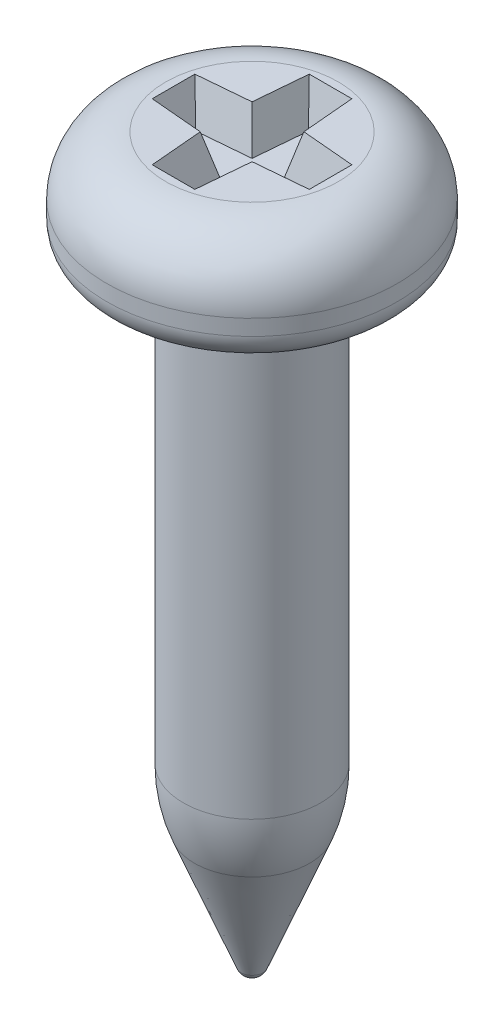
SolidWorks part; units mm, degrees
ref_plane "Front Plane" through (0, 0, 0) normal (0, 0, 1) x (1, 0, 0)
ref_plane "Top Plane" through (0, 0, 0) normal (0, 1, 0) x (1, 0, 0)
ref_plane "Right Plane" through (0, 0, 0) normal (1, 0, 0) x (0, 0, -1)
sketch "Sketch1" plane through (0, 0, 0) normal (0, 0, 1) x (1, 0, 0)
  line L0 (0, 0) -> (0, -9.3) construction
  line L2 (0.875, -6.9644) -> (0.875, -1.45)
  line L3 (1.025, -1.3) -> (1.5, -1.3)
  line L4 (1.85, -0.95) -> (1.85, -0.75)
  line L5 (1.1, 0) -> (0, 0)
  line L6 (0, 0) -> (0, -9.3)
  line L7 (0.7348, -7.7) -> (0.1395, -9.2052)
  arc A0 (1.85, -0.75) -> (1.1, 0) centre (1.1, -0.75) ccw
  arc A1 (1.5, -1.3) -> (1.85, -0.95) centre (1.5, -0.95) ccw
  arc A2 (0.875, -1.45) -> (1.025, -1.3) centre (1.025, -1.45) cw
  arc A3 (0.1395, -9.2052) -> (0, -9.3) centre (0, -9.15) cw
  arc A4 (0.7348, -7.7) -> (0.875, -6.9644) centre (-1.125, -6.9644) ccw
  point P3 (0, 0)
  point P13 (0.875, -1.3)
  point P19 (0, 0)
  point P20 (0, 0)
  point P21 (0, 0)
  point P22 (0.5012, -7.2)
  point P23 (0, 0)
  point P24 (0.9544, -3.2254)
  point P25 (0.8362, -7.4591)
  dimension "D3" = 0.75
  dimension "D6" = 0.35
  dimension "D7" = 0.15
  dimension "D8" = 2
  dimension "D4" = 1.6
  dimension "D10" = 0.15
  dimension "D1" = 3.7
  dimension "D2" = 1.3
  dimension "D5" = 1.75
  dimension "D9" = 8
revolve "Revolve1" add sketch "Sketch1" angle 360 about L0
sketch "Sketch2" plane through (0, 0, 0) normal (0, 1, 0) x (1, 0, 0)
  line L0 (0, 1) -> (0, 0) construction
  line L1 (0, 0) -> (1, 0) construction
  line L2 (-0.2714, 1) -> (0.2714, 1)
  line L3 (0.2714, 1) -> (0.33, 0.33)
  line L4 (0.33, 0.33) -> (1, 0.2714)
  line L5 (1, 0.2714) -> (1, -0.2714)
  line L6 (-1, 0.2714) -> (-1, -0.2714)
  line L7 (-0.33, 0.33) -> (-1, 0.2714)
  line L8 (-0.2714, 1) -> (-0.33, 0.33)
  line L9 (-0.33, -0.33) -> (-1, -0.2714)
  line L10 (-0.2714, -1) -> (-0.33, -0.33)
  line L11 (-0.2714, -1) -> (0.2714, -1)
  line L12 (0.2714, -1) -> (0.33, -0.33)
  line L13 (0.33, -0.33) -> (1, -0.2714)
  point P3 (0, 0)
  point P9 (0.1999, 1.7861)
  point P10 (0, 0)
  point P11 (0.0842, 1.3833)
  point P12 (0.1788, 1.3833)
  point P18 (-1, 0)
  point P26 (0, 0)
  dimension "D1" = 95
  dimension "D2" = 2
  dimension "D3" = 0.66
extrude "Cut-Extrude1" cut sketch "Sketch2" against normal blind 0.5 draft 15
